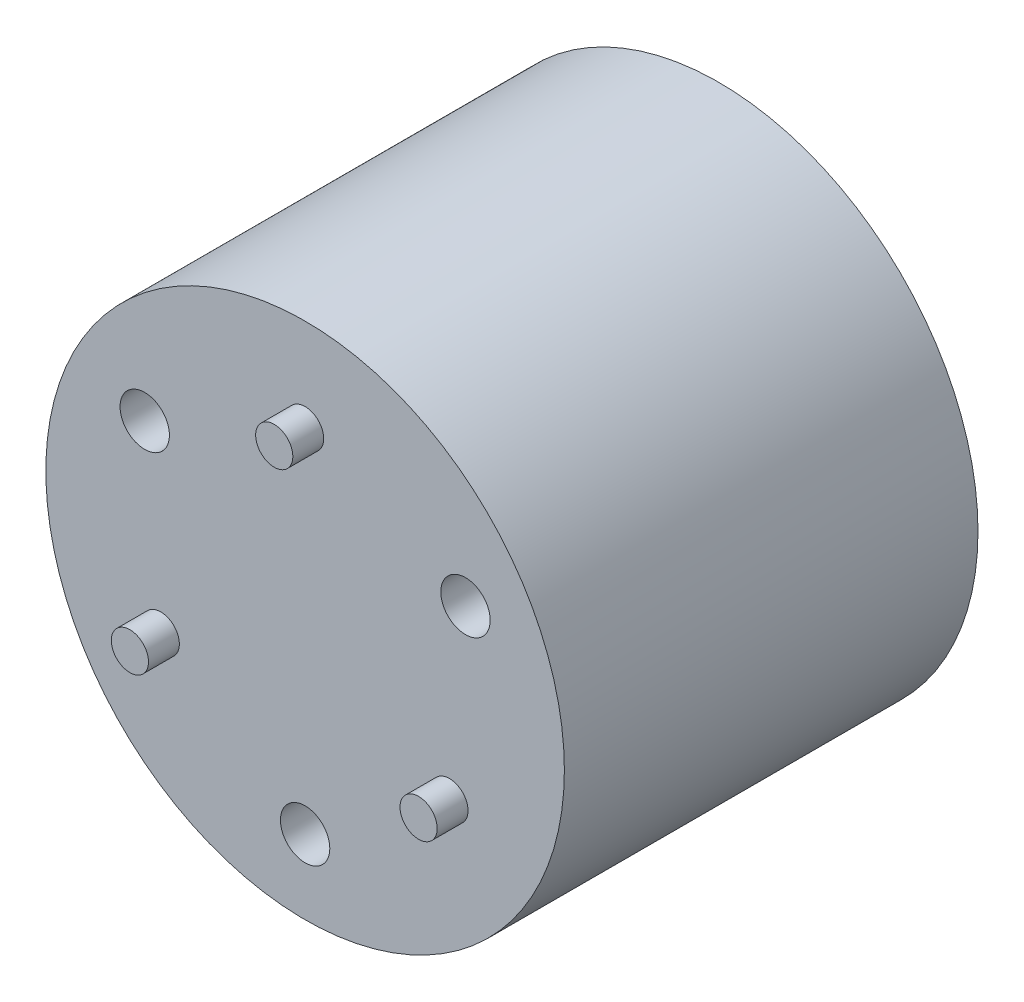
SolidWorks part; units mm, degrees
ref_plane "Front Plane" through (0, 0, 0) normal (0, 0, 1) x (1, 0, 0)
ref_plane "Top Plane" through (0, 0, 0) normal (0, 1, 0) x (1, 0, 0)
ref_plane "Right Plane" through (0, 0, 0) normal (1, 0, 0) x (0, 0, -1)
sketch "Sketch1" plane through (0, 0, 0) normal (1, 0, 0) x (0, 0, -1)
  line L0 (0, 0) -> (31.1882, 0) construction
sketch "Sketch2" plane through (0, 0, 0) normal (0, 0, 1) x (1, 0, 0)
  circle A0 centre (0, 0) radius 21
  point P0 (0, 0)
  dimension "D1" = 42
extrude "Boss-Extrude1" add sketch "Sketch2" against normal blind 33.5
sketch "Sketch3" plane through (0, 0, 0) normal (0, 0, 1) x (1, 0, 0)
  circle A0 centre (0, 0) radius 15 construction
  circle A1 centre (0, -15) radius 2
  circle A2 centre (-12.9904, 7.5) radius 2
  circle A3 centre (12.9904, 7.5) radius 2
  point P3 (0, -15)
  point P12 (0, 0)
  dimension "D1" = 30
  dimension "D2" = 4
  dimension "D3" = 3
extrude "Cut-Extrude2" cut sketch "Sketch3" against normal blind 4
sketch "Sketch4" plane through (0, 0, 0) normal (0, 0, 1) x (1, 0, 0)
  circle A0 centre (0, 0) radius 13.5 construction
  circle A1 centre (0, 13.5) radius 1.5059
  circle A2 centre (11.6913, -6.75) radius 1.5059
  circle A3 centre (-11.6913, -6.75) radius 1.5059
  point P11 (0, 0)
  dimension "D1" = 27
  dimension "D2" = 3
extrude "Boss-Extrude2" add sketch "Sketch4" along normal blind 2.5
sketch "Sketch5" plane through (0, 0, 0) normal (0, 0, 1) x (1, 0, 0)
  point P0 (0, 0)
sketch "Sketch6" plane through (0, 0, -33.5) normal (0, 0, -1) x (-1, 0, 0)
  point P0 (0, 0)
